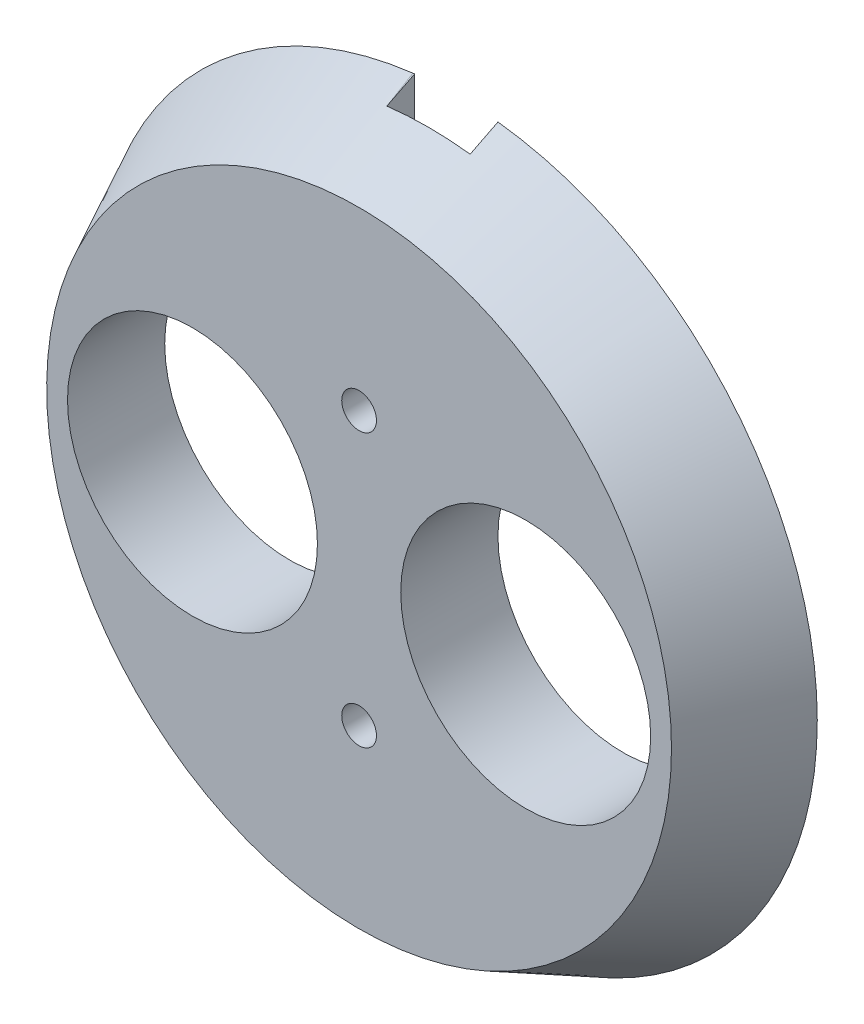
SolidWorks part; units mm, degrees
ref_plane "Front Plane" through (0, 0, 0) normal (0, 0, 1) x (1, 0, 0)
ref_plane "Top Plane" through (0, 0, 0) normal (0, 1, 0) x (1, 0, 0)
ref_plane "Right Plane" through (0, 0, 0) normal (1, 0, 0) x (0, 0, -1)
sketch "Sketch1" plane through (0, 0, 0) normal (0, 0, 1) x (1, 0, 0)
  circle A0 centre (0, 0) radius 26
  dimension "D1" = 52
ref_plane "Plane1" through (0, 0, 7) normal (0, 0, 1) x (1, 0, 0)
sketch "Sketch2" plane through (0, 0, 7) normal (0, 0, 1) x (1, 0, 0)
  circle A0 centre (0, 0) radius 22.5
  dimension "D1" = 45
loft "Loft1" add profiles "Sketch2", "Sketch1" connector at (22.1146, -4.1466, 7) connector at (25.5546, -4.7917, 0)
sketch "Sketch3" plane through (0, 0, 0) normal (0, 0, -1) x (-1, 0, 0)
  line L0 (-26, 0) -> (26, 0) construction
  line L1 (-3, -36.8263) -> (3, -36.8263)
  line L2 (-3, -36.8263) -> (-3, -14.8263)
  line L3 (-3, -14.8263) -> (3, -14.8263)
  line L4 (3, -36.8263) -> (3, -14.8263)
  line L5 (0, 26) -> (0, -26) construction
  line L6 (3, 36.8263) -> (3, 14.8263)
  line L7 (-3, 14.8263) -> (3, 14.8263)
  line L8 (-3, 36.8263) -> (-3, 14.8263)
  line L9 (-3, 36.8263) -> (3, 36.8263)
  circle A0 centre (0, 0) radius 26 construction
  point P11 (0, -14.8263)
  point P12 (-3, -25.8263)
  dimension "D1" = 6
  dimension "D2" = 11
extrude "Cut-Extrude1" cut sketch "Sketch3" against normal blind 2
hole_wizard "M3x0.5 Tapped Hole1" positions "Sketch4" profile "Sketch5" tap size "M3x0.5" standard "ANSI Metric"
sketch "Sketch4" plane through (0, 0, 0) normal (0, 0, -1) x (-1, 0, 0)
  line L0 (3, -14.8263) -> (-3, -14.8263) construction
  line L1 (-26, 0) -> (26, 0) construction
  arc A0 (-3, 25.8263) -> (-3, -25.8263) centre (0, 0) ccw construction
  arc A1 (3, -25.8263) -> (3, 25.8263) centre (0, 0) ccw construction
  point P2 (0, -9.825)
  point P9 (0, -14.8263)
  point P21 (0, 9.825)
  dimension "D1" = 9.825
sketch "Sketch5" plane through (0, -9.825, 0) normal (1, 0, 0) x (0, 1, 0)
  line L0 (0, 0) -> (0, 8.2511)
  line L1 (0, 8.2511) -> (1.25, 7.5)
  line L2 (1.25, 7.5) -> (1.25, 0)
  line L5 (1.25, 0) -> (0, 0)
  line L10 (0, 8.2511) -> (-1.25, 7.5) construction
  line L11 (0, -6.35) -> (0, 107.95) construction
  dimension "Tap Drill Dia." = 2.5
  dimension "Tap Drill Depth" = 7.5
  dimension "Drill Angle" = 118
hole_wizard "M18 Clearance Hole1" positions "Sketch6" profile "Sketch7" hole size "M18" standard "ANSI Metric" end condition through all
sketch "Sketch6" plane through (0, 0, 0) normal (0, 0, -1) x (-1, 0, 0)
  line L0 (0, 14.8263) -> (0, -14.8263) construction
  line L1 (-3, 14.8263) -> (3, 14.8263) construction
  line L2 (3, -14.8263) -> (-3, -14.8263) construction
  line L4 (26, 0) -> (-26, 0) construction
  arc A0 (3, -25.8263) -> (3, 25.8263) centre (0, 0) ccw construction
  arc A1 (-3, 25.8263) -> (-3, -25.8263) centre (0, 0) ccw construction
  point P0 (-12, 0)
  point P21 (12, 0)
  dimension "D1" = 12
sketch "Sketch7" plane through (12, 0, 0) normal (1, 0, 0) x (0, 1, 0)
  line L0 (0, 0) -> (0, 7.0001)
  line L1 (0, 7.0001) -> (9, 7.0001)
  line L2 (9, 7.0001) -> (9, 0)
  line L5 (9, 0) -> (0, 0)
  line L11 (0, -6.35) -> (0, 107.95) construction
  dimension "Thru Hole Dia." = 18
  dimension "Thru Hole Depth" = 7.0001
